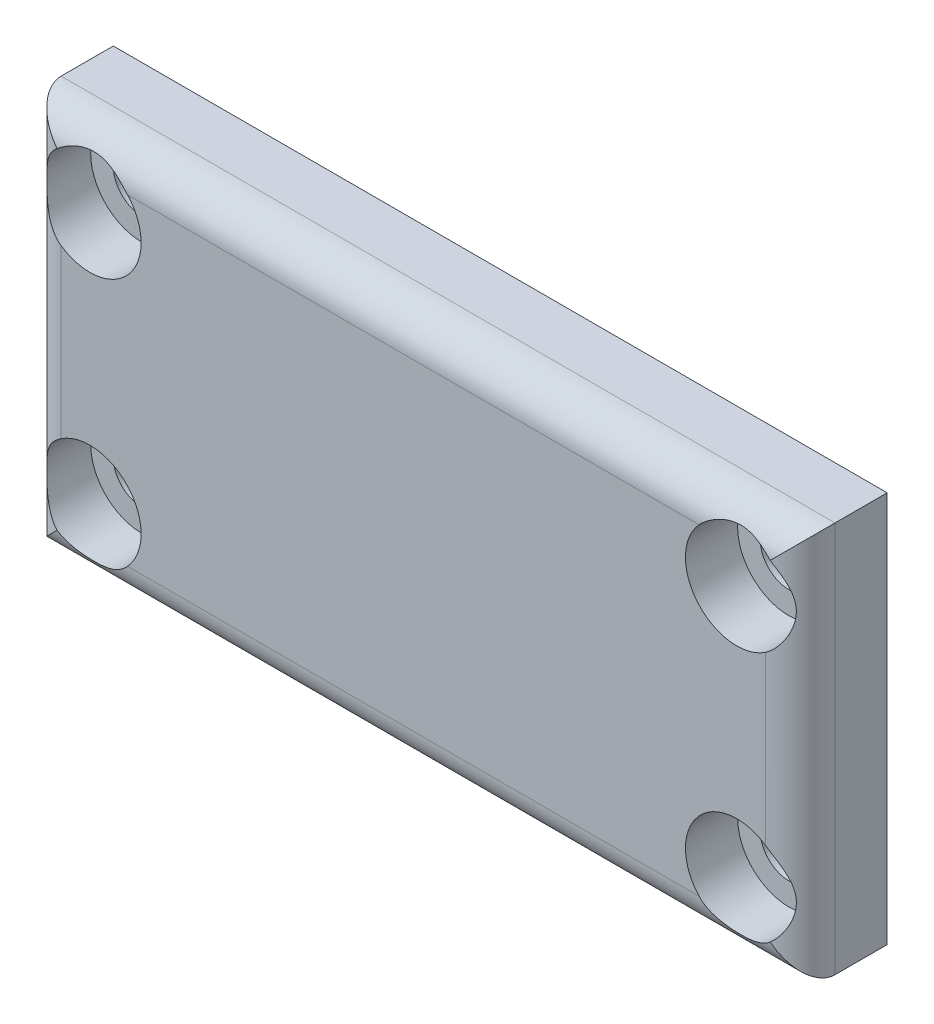
SolidWorks part; units mm, degrees
ref_plane "Ebene vorne" through (0, 0, 0) normal (0, 0, 1) x (1, 0, 0)
ref_plane "Ebene oben" through (0, 0, 0) normal (0, 1, 0) x (1, 0, 0)
ref_plane "Ebene rechts" through (0, 0, 0) normal (1, 0, 0) x (0, 0, -1)
sketch "Skizze1" plane through (0, 0, 0) normal (0, 0, 1) x (1, 0, 0)
  line L0 (0, 0) -> (0, 4.2847) construction
  line L1 (-22.25, -11.25) -> (22.25, -11.25)
  line L2 (-22.25, -11.25) -> (-22.25, 11.25)
  line L3 (-22.25, 11.25) -> (22.25, 11.25)
  line L4 (22.25, -11.25) -> (22.25, 11.25)
  line L5 (-22.25, -11.25) -> (22.25, 11.25) construction
  line L6 (-22.25, 11.25) -> (22.25, -11.25) construction
  line L7 (0, 4.2847) -> (0, 0) construction
  line L8 (0, 0) -> (-8.294, 0) construction
  circle A0 centre (-18.6, 7.25) radius 1.65
  circle A1 centre (18.6, 7.25) radius 1.65
  circle A2 centre (18.6, -7.25) radius 1.65
  circle A3 centre (-18.6, -7.25) radius 1.65
  point P0 (0, 0)
  dimension "D5" = 3.3
  dimension "D1" = 44.5
  dimension "D2" = 22.5
  dimension "D3" = 4
  dimension "D4" = 3.65
extrude "Aufsatz-Linear austragen1" add sketch "Skizze1" along normal blind 5
fillet "Verrundung1" radius 2 4 edges at (-22.25, 0, 5) (0, -11.25, 5) (22.25, 0, 5) (0, 11.25, 5)
sketch "Skizze2" plane through (0, 0, 5) normal (0, 0, 1) x (1, 0, 0)
  line L0 (0, 0) -> (0, 2.0793) construction
  line L1 (0, 2.0793) -> (0, 0) construction
  line L2 (0, 0) -> (-1.7706, 0) construction
  circle A0 centre (-18.6, 7.25) radius 2.95
  circle A1 centre (-18.6, -7.25) radius 2.95
  circle A2 centre (18.6, -7.25) radius 2.95
  circle A3 centre (18.6, 7.25) radius 2.95
  dimension "D1" = 5.9
extrude "Schnitt-Linear austragen1" cut sketch "Skizze2" against normal offset from surface (3 mm away) 2 up to face at (20.25, -7.25, 0)
